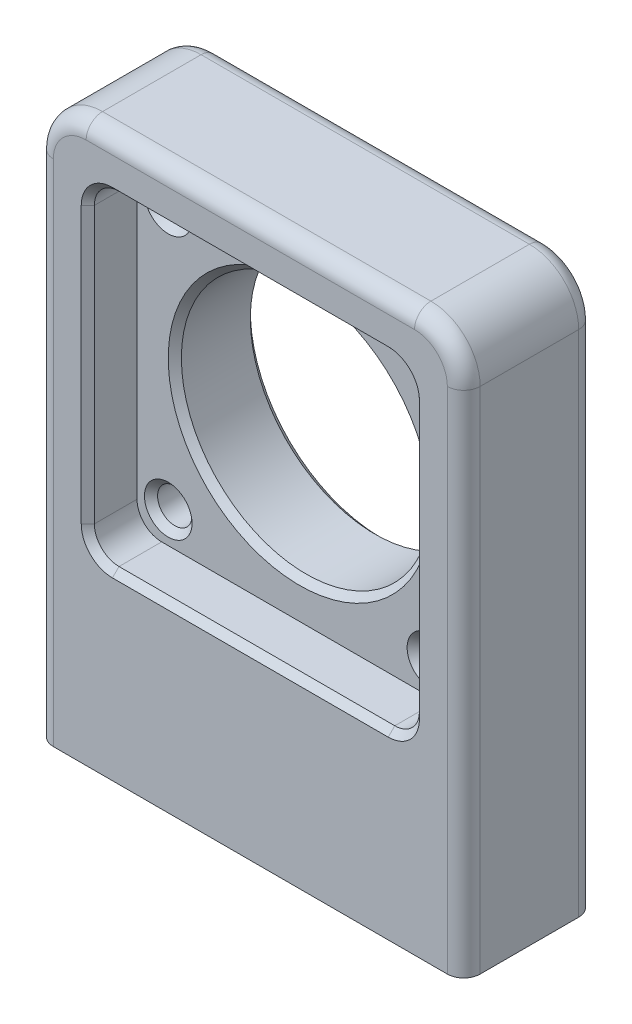
SolidWorks part; units mm, degrees
ref_plane "Front Plane" through (0, 0, 0) normal (0, 0, 1) x (1, 0, 0)
ref_plane "Top Plane" through (0, 0, 0) normal (0, 1, 0) x (1, 0, 0)
ref_plane "Right Plane" through (0, 0, 0) normal (1, 0, 0) x (0, 0, -1)
sketch "Sketch1" plane through (0, 0, 0) normal (0, 0, 1) x (1, 0, 0)
  line L1 (-13, 17) -> (13, 17)
  line L2 (-13, 17) -> (-13, -17)
  line L3 (-13, -17) -> (13, -17)
  line L4 (13, 17) -> (13, -17)
  line L5 (-13, 17) -> (13, -17) construction
  line L6 (-13, -17) -> (13, 17) construction
  point P0 (0, 0)
  dimension "D1" = 26
  dimension "D2" = 34
extrude "Boss-Extrude1" add sketch "Sketch1" along normal blind 8
sketch "Sketch2" plane through (0, 0, 8) normal (0, 0, 1) x (1, 0, 0)
  line L0 (0, 11.6) -> (0, -3.6) construction
  line L1 (-7.6, 4) -> (7.6, 4) construction
  line L2 (0, 17) -> (0, 12.6484) construction
  line L3 (13, 17) -> (-13, 17) construction
  circle A0 centre (0, 4) radius 7.6
  circle A1 centre (-8, 12) radius 1.05
  circle A2 centre (8, 12) radius 1.05
  circle A3 centre (8, -4) radius 1.05
  circle A4 centre (-8, -4) radius 1.05
  dimension "D1" = 15.2
  dimension "D4" = 2.1
  dimension "D5" = 13
  dimension "D2" = 8
  dimension "D3" = 8
extrude "Cut-Extrude1" cut sketch "Sketch2" against normal up to next
sketch "Sketch5" plane through (0, -17, 0) normal (0, -1, 0) x (1, 0, 0)
  line L0 (13, 4) -> (-13, 4) construction
  line L1 (13, 8) -> (13, 0) construction
  line L2 (-13, 8) -> (-13, 0) construction
  line L3 (0, 0) -> (0, 8) construction
  line L4 (-13, 0) -> (13, 0) construction
  line L5 (-13, 8) -> (13, 8) construction
  circle A0 centre (6, 4) radius 2.3
  circle A1 centre (-6, 4) radius 2.3
  dimension "D1" = 4.6
  dimension "D2" = 6
extrude "Cut-Extrude7" cut sketch "Sketch5" against normal blind 4.5
sketch "Sketch6" plane through (0, 0, 8) normal (0, 0, 1) x (1, 0, 0)
  line L1 (-9.9, 13.9) -> (9.9, 13.9)
  line L2 (-9.9, 13.9) -> (-9.9, -5.9)
  line L3 (-9.9, -5.9) -> (9.9, -5.9)
  line L4 (9.9, 13.9) -> (9.9, -5.9)
  line L5 (-9.9, 13.9) -> (9.9, -5.9) construction
  line L6 (-9.9, -5.9) -> (9.9, 13.9) construction
  point P0 (0, 4)
  dimension "D2" = 19.8
extrude "Cut-Extrude8" cut sketch "Sketch6" against normal blind 3
sketch "Sketch7" plane through (0, 0, 0) normal (0, 0, -1) x (-1, 0, 0)
  circle A0 centre (-8, 12) radius 1.9
  circle A1 centre (8, 12) radius 1.9
  circle A2 centre (-8, -4) radius 1.9
  circle A3 centre (8, -4) radius 1.9
  dimension "D1" = 3.8
extrude "Cut-Extrude9" cut sketch "Sketch7" against normal blind 3
fillet "Fillet1" radius 3 2 edges at (13, 17, 4) (-13, 17, 4)
chamfer "Chamfer3" distance 0.4 angle 45 4 edges at (6, -12.5, 1.7) (-6, -12.5, 6.3) (-6, -17, 6.3) (6, -17, 1.7)
fillet "Fillet2" radius 1.5 4 edges at (-9.9, -5.9, 6.5) (9.9, -5.9, 6.5) (9.9, 13.9, 6.5) (-9.9, 13.9, 6.5)
chamfer "Chamfer7" distance 1 angle 45 4 edges at (-9.9, 12, 3) (6.1, 12, 3) (6.1, -4, 3) (-9.9, -4, 3)
chamfer "Chamfer9" distance 0.4 angle 45 14 edges at (7.6, 4, 5) (7.6, 4, 0) (0, -5.9, 8) (9.4607, -5.4607, 8) (-9.4607, -5.4607, 8) (9.9, 4, 8) (-9.9, 4, 8) (9.4607, 13.4607, 8) (-9.4607, 13.4607, 8) (0, 13.9, 8) (-9.9, 12, 0) (6.1, 12, 0) (6.1, -4, 0) (-9.9, -4, 0)
chamfer "Chamfer10" distance 0.4 angle 45 4 edges at (9.05, -4, 5) (9.05, 12, 5) (-6.95, 12, 5) (-6.95, -4, 5)
fillet "Fillet4" radius 1 10 edges at (13, -1.5, 8) (12.1213, 16.1213, 8) (0, 17, 8) (-12.1213, 16.1213, 8) (-13, -1.5, 8) (-13, -1.5, 0) (-12.1213, 16.1213, 0) (0, 17, 0) (12.1213, 16.1213, 0) (13, -1.5, 0)
